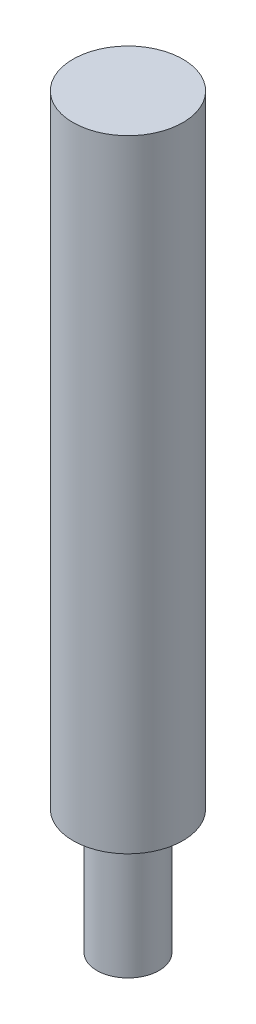
SolidWorks part; units mm, degrees
material "黄铜"
ref_plane "前视基准面" through (0, 0, 0) normal (0, 0, 1) x (1, 0, 0)
ref_plane "上视基准面" through (0, 0, 0) normal (0, 1, 0) x (1, 0, 0)
ref_plane "右视基准面" through (0, 0, 0) normal (1, 0, 0) x (0, 0, -1)
sketch "草图1" plane through (0, 0, 0) normal (0, 1, 0) x (1, 0, 0)
  circle A0 centre (0, 0) radius 1.5
  dimension "D1" = 3
extrude "凸台-拉伸1" add sketch "草图1" along normal blind 6
sketch "草图2" plane through (0, 6, 0) normal (0, 1, 0) x (1, 0, 0)
  circle A0 centre (0, 0) radius 2.65
  dimension "D1" = 5.3
extrude "凸台-拉伸2" add sketch "草图2" along normal blind 30
